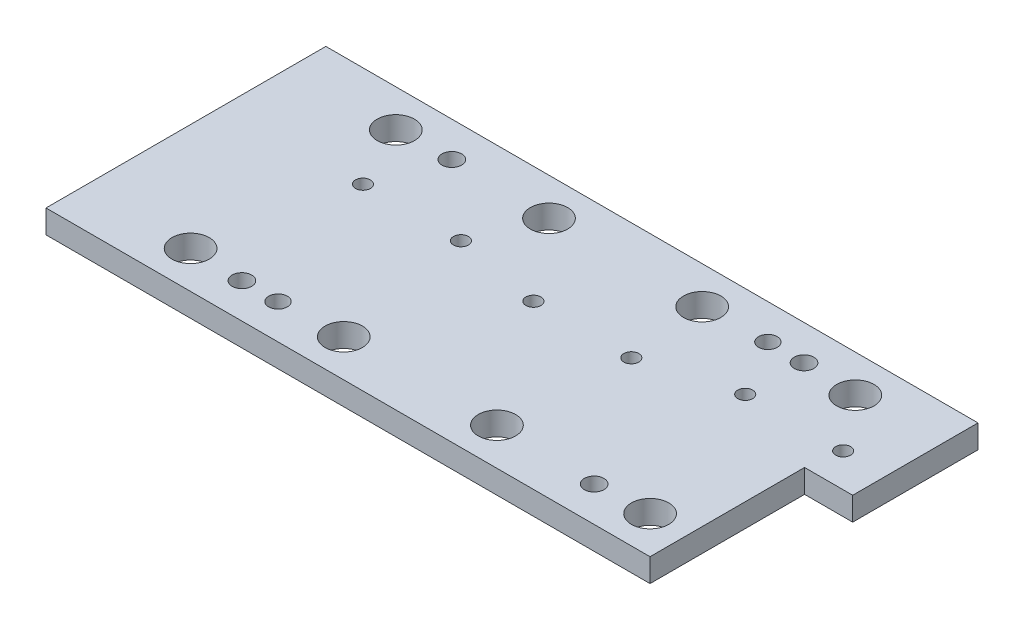
SolidWorks part; units mm, degrees
material "K110"
ref_plane "Front Plane" through (0, 0, 0) normal (0, 0, 1) x (1, 0, 0)
ref_plane "Top Plane" through (0, 0, 0) normal (0, 1, 0) x (1, 0, 0)
ref_plane "Right Plane" through (0, 0, 0) normal (1, 0, 0) x (0, 0, -1)
sketch "Sketch1" plane through (0, 0, 0) normal (0, 1, 0) x (1, 0, 0)
  line L0 (-229, 60) -> (-229, -60) construction
  line L1 (-229, -60) -> (0, -60)
  line L2 (-229, -60) -> (-229, 60)
  line L3 (-229, 60) -> (0, 60)
  line L4 (0, -60) -> (0, 60)
  point P4 (0, 0)
  dimension "D1" = 120
extrude "Boss-Extrude1" add sketch "Sketch1" along normal mid plane 10
sketch "Sketch4" plane through (0, 5, 0) normal (0, 1, 0) x (1, 0, 0)
  line L1 (0, 60) -> (20.6325, 60)
  line L2 (0, 60) -> (0, 6.27)
  line L3 (0, 6.27) -> (20.6325, 6.27)
  line L4 (20.6325, 60) -> (20.6325, 6.27)
extrude "Boss-Extrude2" add sketch "Sketch4" against normal up to surface (10 mm away) up to face at (-114.5, -5, 0)
hole_wizard "Ø16.0 (16) Diameter Hole1" positions "Sketch7" profile "Sketch6" hole size "Ø16.0" standard "ISO" end condition through all
sketch "Sketch7" plane through (0, 5, 0) normal (0, 1, 0) x (1, 0, 0)
  point P0 (-213, 44)
  point P3 (-147.323, 44)
  point P6 (-81.646, 44)
  point P9 (-15.969, 44)
  point P12 (-213, -44)
  point P15 (-147.323, -44)
  point P18 (-81.646, -44)
  point P21 (-15.969, -44)
sketch "Sketch6" plane through (-213, 5, -44) normal (1, 0, 0) x (0, 0, 1)
  line L0 (0, 0) -> (0, 10)
  line L1 (0, 10) -> (8, 10)
  line L2 (8, 10) -> (8, 0)
  line L5 (8, 0) -> (0, 0)
  line L11 (0, -6.35) -> (0, 107.95) construction
  dimension "Thru Hole Dia." = 16
  dimension "Thru Hole Depth" = 10
hole_wizard "M6 Clearance Hole1" positions "Sketch12" profile "Sketch11" hole size "M6" standard "ISO" end condition through all
sketch "Sketch12" plane through (0, 5, 0) normal (0, 1, 0) x (1, 0, 0)
  point P0 (-199.875, 16.78)
  point P3 (-157.875, 16.78)
  point P6 (-119.875, 9.8524)
  point P9 (-77.875, 9.8524)
  point P12 (-39.875, 20.691)
  point P15 (2.125, 20.691)
sketch "Sketch11" plane through (-199.875, 5, -16.78) normal (1, 0, 0) x (0, 0, 1)
  line L0 (0, 0) -> (0, 10)
  line L1 (0, 10) -> (3.2, 10)
  line L2 (3.2, 10) -> (3.2, 0)
  line L5 (3.2, 0) -> (0, 0)
  line L11 (0, -6.35) -> (0, 107.95) construction
  dimension "Thru Hole Dia." = 6.4
  dimension "Thru Hole Depth" = 10
hole_wizard "M8 Clearance Hole1" positions "Sketch15" profile "Sketch14" hole size "M8" standard "ISO" end condition through all
sketch "Sketch15" plane through (0, 5, 0) normal (0, 1, 0) x (1, 0, 0)
  point P0 (-190, -45)
  point P3 (-38.969, -45)
  point P6 (-38.969, 45)
  point P9 (-190, 45)
sketch "Sketch14" plane through (-190, 5, 45) normal (1, 0, 0) x (0, 0, 1)
  line L0 (0, 0) -> (0, 10)
  line L1 (0, 10) -> (4.2, 10)
  line L2 (4.2, 10) -> (4.2, 0)
  line L5 (4.2, 0) -> (0, 0)
  line L11 (0, -6.35) -> (0, 107.95) construction
  dimension "Thru Hole Dia." = 8.4
  dimension "Thru Hole Depth" = 10
hole_wizard "Ø8.0mm Dowel Hole1" positions "Sketch18" profile "Sketch17" hole size "Ø8.0" standard "ISO" end condition through all
sketch "Sketch18" plane through (0, 5, 0) normal (0, 1, 0) x (1, 0, 0)
  point P0 (-54.469, 45)
  point P3 (-174.5, -45)
sketch "Sketch17" plane through (-54.469, 5, -45) normal (1, 0, 0) x (0, 0, 1)
  line L0 (0, 0) -> (0, 10)
  line L1 (0, 10) -> (4, 10)
  line L2 (4, 10) -> (4, 0)
  line L5 (4, 0) -> (0, 0)
  line L11 (0, -6.35) -> (0, 107.95) construction
  dimension "Thru Hole Dia." = 8
  dimension "Thru Hole Depth" = 10
sketch "Sketch20" plane through (-229, 0, 0) normal (-1, 0, 0) x (0, 0, 1)
  line L4 (-60, -5) -> (60, -5)
  line L5 (60, -5) -> (60, 5)
  line L6 (60, 5) -> (-60, 5)
  line L7 (-60, 5) -> (-60, -5)
  line L8 (-60, -5) -> (60, -5)
  line L9 (60, -5) -> (60, 5)
  line L10 (60, 5) -> (-60, 5)
  line L11 (-60, 5) -> (-60, -5)
  dimension "D1" = 0
extrude "Boss-Extrude3" add sketch "Sketch20" along normal blind 30
